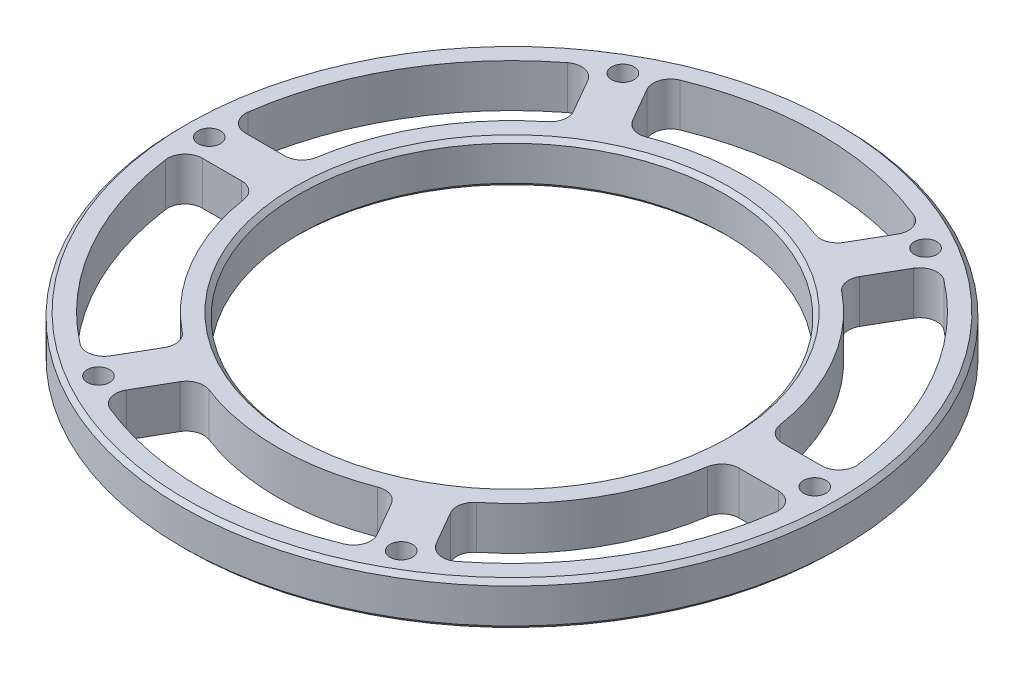
SolidWorks part; units mm, degrees
material "6061-T6 (SS)"
ref_plane "Front Plane" through (0, 0, 0) normal (0, 0, 1) x (1, 0, 0)
ref_plane "Top Plane" through (0, 0, 0) normal (0, 1, 0) x (1, 0, 0)
ref_plane "Right Plane" through (0, 0, 0) normal (1, 0, 0) x (0, 0, -1)
sketch "Sketch2" plane through (0, 0, 0) normal (1, 0, 0) x (0, 0, -1)
  line L0 (-49.2125, 0) -> (-76.2, 0)
  line L1 (-76.2, 0) -> (-76.2, 10)
  line L2 (-76.2, 10) -> (-49.2125, 10)
  line L3 (-49.2125, 10) -> (-49.2125, 0)
  dimension "D1" = 76.2
  dimension "D2" = 10
  dimension "D4" = 49.2125
ref_axis "Axis1" through (0, -0.5, 0) along (0, 1, 0)
revolve "Revolve1" add sketch "Sketch2" angle 360 about axis through (0, -0.5, 0) along (0, 1, 0)
hole_wizard "#6 (0.204) Diameter Hole1" positions "Sketch6" profile "Sketch7" hole size "#6" standard "ANSI Inch" end condition through all
sketch "Sketch6" plane through (0, 10, 0) normal (0, 1, 0) x (1, 0, 0)
  line L0 (0, 0) -> (-69.8201, 120.932) construction
  line L2 (0, 0) -> (0, 109.0908) construction
  point P0 (-35, 60.6218)
  dimension "D1" = 30
  dimension "D2" = 70
sketch "Sketch7" plane through (-35, 10, -60.6218) normal (1, 0, 0) x (0, 0, 1)
  line L0 (0, 0) -> (0, 10)
  line L1 (0, 10) -> (2.5908, 10)
  line L2 (2.5908, 10) -> (2.5908, 0)
  line L5 (2.5908, 0) -> (0, 0)
  line L11 (0, -6.35) -> (0, 107.95) construction
  dimension "Thru Hole Dia." = 5.1816
  dimension "Thru Hole Depth" = 10
pattern_circular "CirPattern3" count 6 over 360 about axis through (0, -0.5, 0) along (0, 1, 0) of "#6 (0.204) Diameter Hole1"
sketch "Sketch8" plane through (0, 10, 0) normal (0, 1, 0) x (1, 0, 0)
  line L4 (0, 0) -> (0, 93.9995) construction
  line L5 (-22.6606, 49.2493) -> (-31.182, 64.0088)
  line L6 (22.6606, 49.2493) -> (31.182, 64.0088)
  line L7 (0, 0) -> (-35, 60.6218) construction
  arc A0 (-22.6606, 49.2493) -> (22.6606, 49.2493) centre (0, 0) cw
  arc A1 (-31.182, 64.0088) -> (31.182, 64.0088) centre (0, 0) cw
  circle A2 centre (0, 0) radius 76.2 construction
  circle A4 centre (0, 0) radius 49.2125 construction
  dimension "D1" = 5
  dimension "D2" = 5
  dimension "D3" = 5
extrude "Cut-Extrude1" cut sketch "Sketch8" against normal through all
fillet "Fillet1" radius 4 4 edges at (-22.6606, 5, -49.2493) (22.6606, 5, -49.2493) (31.182, 5, -64.0088) (-31.182, 5, -64.0088)
pattern_circular "CirPattern4" count 6 over 360 about axis through (0, -0.5, 0) along (0, 1, 0) of "Cut-Extrude1", "Fillet1"
chamfer "Chamfer1" distance 1 angle 45 2 edges at (0, 10, -49.2125) (0, 0, -49.2125)
chamfer "Chamfer2" distance 1 angle 45 2 edges at (0, 10, -76.2) (0, 0, -76.2)
equation "\"TubeDiameter\"= 6.000in"
equation "\"D1@Sketch2\"=\"TubeDiameter\"/2"
